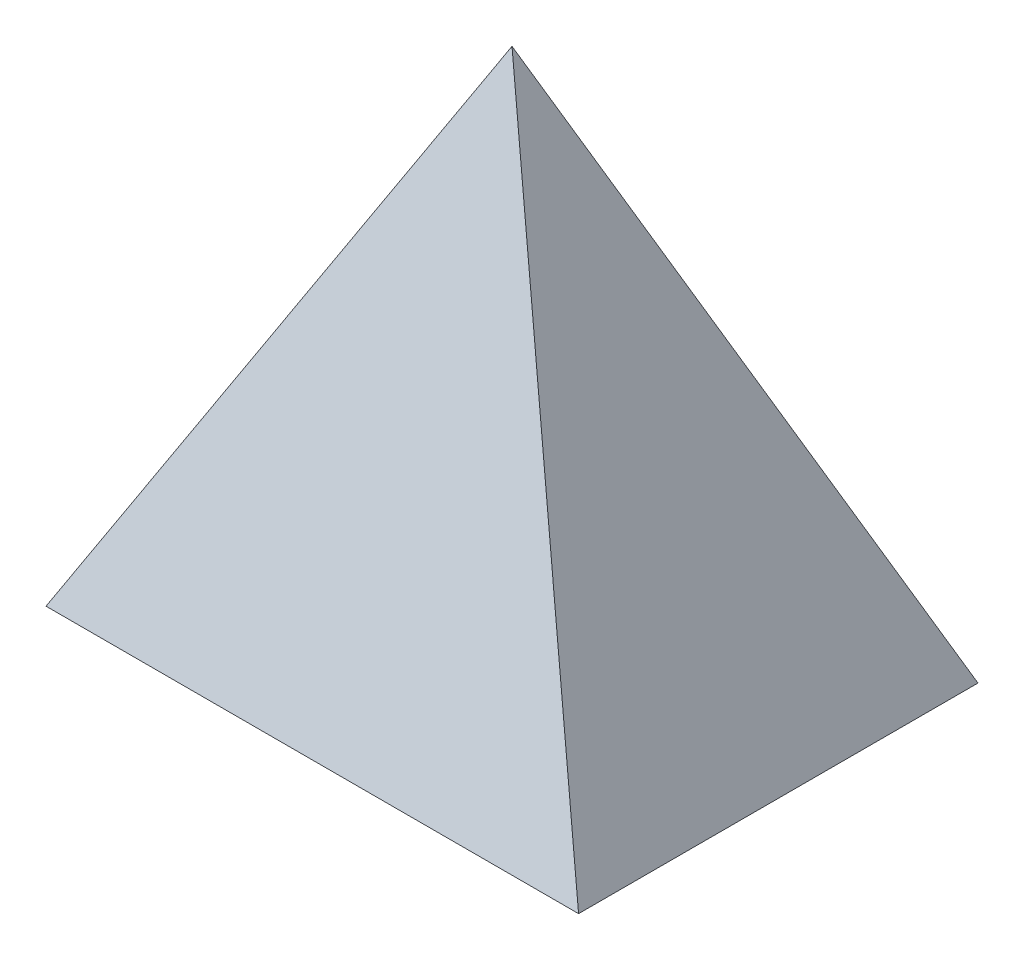
SolidWorks part; units mm, degrees
ref_plane "Front Plane" through (0, 0, 0) normal (0, 0, 1) x (1, 0, 0)
ref_plane "Top Plane" through (0, 0, 0) normal (0, 1, 0) x (1, 0, 0)
ref_plane "Right Plane" through (0, 0, 0) normal (1, 0, 0) x (0, 0, -1)
sketch "Sketch5" plane through (0, 0, 0) normal (0, 0, 1) x (1, 0, 0)
  line L0 (0, 0) -> (0, -137.5785) construction
  line L1 (0, 0) -> (-152.4, -296.5383)
  line L2 (0, 0) -> (152.4, -296.5383)
  line L3 (-152.4, -296.5383) -> (152.4, -296.5383)
  dimension "D1" = 54.4
  dimension "D2" = 304.8
extrude "Boss-Extrude6" add sketch "Sketch5" along normal mid plane 228.6 separate body
sketch "Sketch8" plane through (0, 0, 0) normal (1, 0, 0) x (0, 0, -1)
  line L0 (0, 0) -> (-114.3, -296.5383)
  line L1 (-114.3, 0) -> (114.3, 0) construction
  line L2 (0, 0) -> (114.3, -296.5383)
  line L3 (0, 0) -> (-114.3, 0)
  line L4 (-114.3, 0) -> (-114.3, -296.5383)
  line L5 (0, 0) -> (114.3, 0)
  line L6 (114.3, 0) -> (114.3, -296.5383)
extrude "Cut-Extrude1" cut sketch "Sketch8" against normal through all both and the other way through all contours L3 L4 L0 | L6 L5 L2 region at (0, -98.8461, -76.2) region at (0, -98.8461, 76.2)
